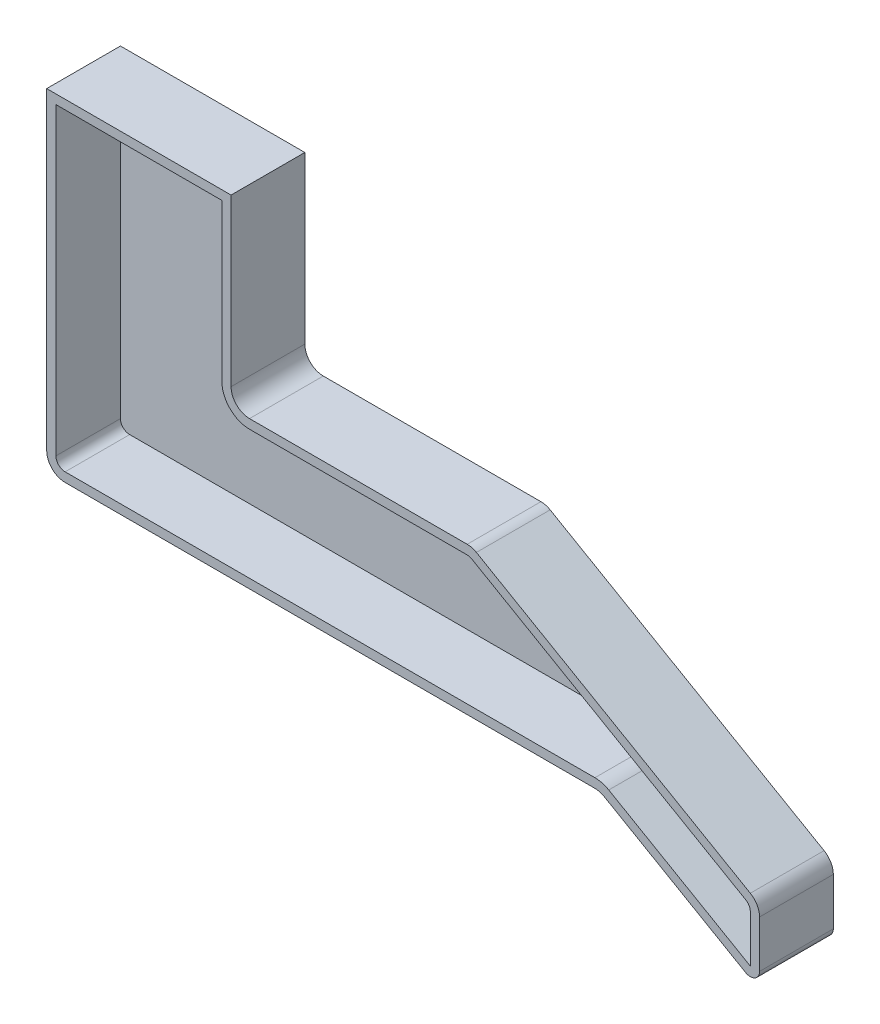
SolidWorks part; units mm, degrees
ref_plane "Front Plane" through (0, 0, 0) normal (0, 0, 1) x (1, 0, 0)
ref_plane "Top Plane" through (0, 0, 0) normal (0, 1, 0) x (1, 0, 0)
ref_plane "Right Plane" through (0, 0, 0) normal (1, 0, 0) x (0, 0, -1)
sketch "Sketch1" plane through (0, 0, 0) normal (0, 0, 1) x (1, 0, 0)
  line L0 (0, 0) -> (50, 0)
  line L1 (50, 0) -> (50, -45)
  line L2 (55, -50) -> (114.0192, -50)
  line L3 (0, 0) -> (0, -85)
  line L4 (5, -90) -> (148.6603, -90)
  line L5 (151.1603, -90.6699) -> (189.5513, -112.8349)
  line L6 (190.8013, -93.5566) -> (116.5192, -50.6699)
  line L7 (193.3013, -97.8868) -> (193.3013, -110.6699)
  line L8 (193.3013, -115) -> (192.7225, -114.3456)
  arc A0 (189.5513, -112.8349) -> (193.3013, -110.6699) centre (190.8013, -110.6699) ccw
  arc A1 (190.8013, -93.5566) -> (193.3013, -97.8868) centre (188.3013, -97.8868) cw
  arc A2 (148.6603, -90) -> (151.1603, -90.6699) centre (148.6603, -95) cw
  arc A3 (114.0192, -50) -> (116.5192, -50.6699) centre (114.0192, -55) cw
  arc A4 (50, -45) -> (55, -50) centre (55, -45) ccw
  arc A5 (0, -85) -> (5, -90) centre (5, -85) ccw
  point P15 (193.3013, -95)
  point P18 (150, -90)
  point P25 (0, -90)
  dimension "D3" = 2.5
  dimension "D8" = 5
  dimension "D1" = 90
  dimension "D2" = 150
  dimension "D4" = 40
  dimension "D5" = 20
  dimension "D6" = 210
  dimension "D7" = 50
  dimension "D9" = 90
  dimension "D10" = 50
extrude "Extrude1" add sketch "Sketch1" along normal blind 20 contours L3 A5 L4 A2 L5 A0 L7 A1 L6 A3 L2 A4 L1 L0 region at (67.937, -60.146, 0)
shell "Shell1" thickness 2.5 removed face at (104.0383, -69.1984, 20)
shell "Shell2" [suppressed] thickness 2.5
sketch "Sketch2" plane through (0, 0, 2.5) normal (0, 0, 1) x (1, 0, 0)
  line L0 (0, 0) -> (50, 0) construction
  line L1 (0, 0) -> (0, -85) construction
  circle A0 centre (15, -10) radius 2.5
  circle A1 centre (35, -10) radius 2.5
  dimension "D2" = 5
  dimension "D3" = 5
  dimension "D1" = 10
  dimension "D4" = 10
  dimension "D5" = 20
  dimension "D6" = 15
extrude "Extrude2" cut sketch "Sketch2" against normal through all
sketch "Sketch3" [suppressed] plane through (0, 0, 17.5) normal (0, 0, -1) x (-1, 0, 0)
  line L0 (0, 0) -> (-50, 0) construction
  line L1 (0, 0) -> (0, -85) construction
  circle A0 centre (-35, -10) radius 2.5
  circle A1 centre (-15, -10) radius 2.5
  dimension "D4" = 5
  dimension "D5" = 5
  dimension "D1" = 20
  dimension "D2" = 10
  dimension "D3" = 10
  dimension "D6" = 15
extrude "Extrude3" [suppressed] cut sketch "Sketch3" against normal through all
